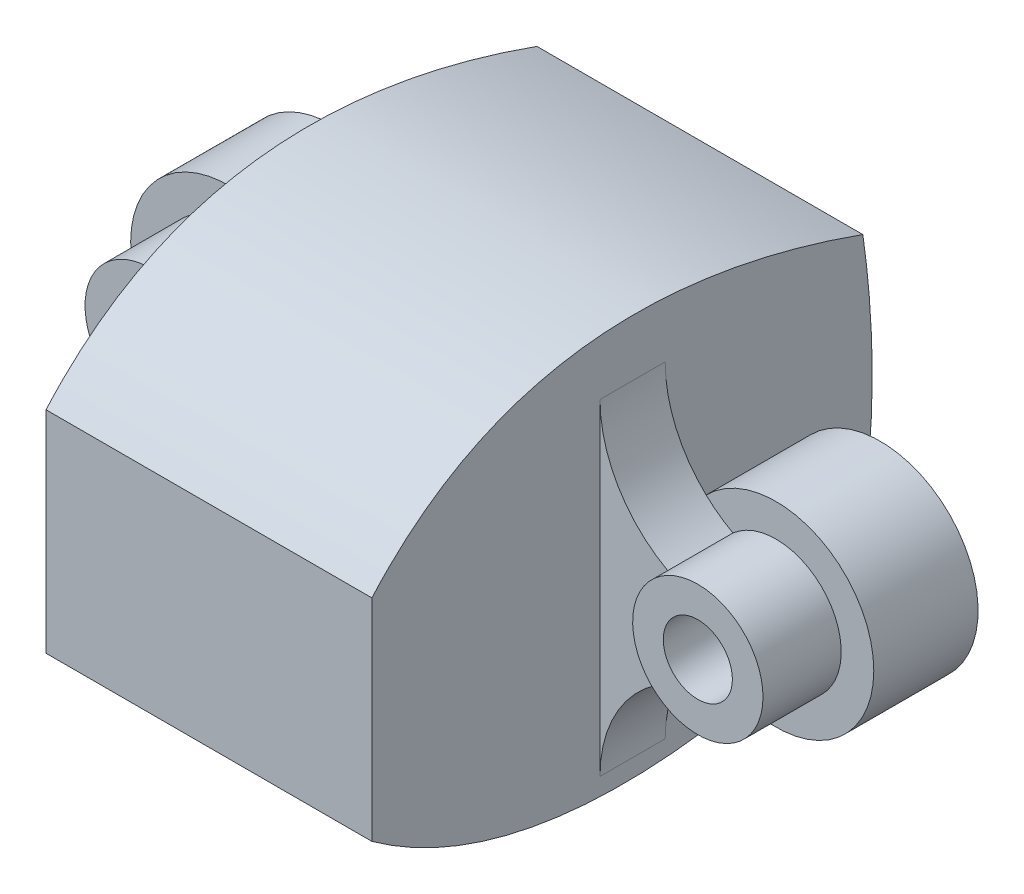
SolidWorks part; units mm, degrees
ref_plane "Front Plane" through (0, 0, 0) normal (0, 0, 1) x (1, 0, 0)
ref_plane "Top Plane" through (0, 0, 0) normal (0, 1, 0) x (1, 0, 0)
ref_plane "Right Plane" through (0, 0, 0) normal (1, 0, 0) x (0, 0, -1)
sketch "Sketch1" plane through (0, 0, 0) normal (1, 0, 0) x (0, 0, -1)
  line L0 (-19.0962, 121.2258) -> (-19.0962, 137.4045)
  spline S0 degree 2 poles (-19.0962, 137.4045) (-6.4675, 151.6991) (18.5686, 142.7118) knots 0 0 0 1 1 1
  spline S1 degree 2 poles (18.5686, 142.7118) (20.5155, 129.0566) (17.199, 118.5721) knots 0 0 0 1 1 1
  spline S2 degree 3 poles (17.199, 118.5721) (7.3552, 114.9342) (-7.5425, 112.8814) (-19.0962, 121.2258) knots 0 0 0 0 1 1 1 1
extrude "Boss-Extrude1" add sketch "Sketch1" along normal mid plane 25
sketch "Sketch3" plane through (0, 0, 0) normal (1, 0, 0) x (0, 0, -1)
  line L0 (0.9038, 129.3152) -> (-19.0962, 129.3152) construction
  line L1 (3.4038, 125.5652) -> (-1.5962, 125.5652)
  line L2 (3.4038, 125.5652) -> (3.4038, 133.0652)
  line L3 (3.4038, 133.0652) -> (-1.5962, 133.0652)
  line L4 (-1.5962, 125.5652) -> (-1.5962, 133.0652)
  line L5 (3.4038, 125.5652) -> (-1.5962, 133.0652) construction
  line L6 (3.4038, 133.0652) -> (-1.5962, 125.5652) construction
  line L7 (-19.0962, 137.4045) -> (-19.0962, 121.2258) construction
  point P4 (0.9038, 129.3152)
  dimension "D1" = 7.5
  dimension "D2" = 5
  dimension "D3" = 20
extrude "Boss-Extrude2" add sketch "Sketch3" along normal mid plane 55
sketch "Sketch4" plane through (0, 0, -3.4038) normal (0, 0, -1) x (-1, 0, 0)
  line L0 (-27.5, 129.3152) -> (27.5, 129.3152) construction
  line L1 (-27.5, 125.5652) -> (-27.5, 133.0652) construction
  line L2 (27.5, 125.5652) -> (27.5, 133.0652) construction
  circle A0 centre (-21.0048, 129.3152) radius 7.5
  circle A1 centre (21.0048, 129.3152) radius 7.5
  dimension "D1" = 15
extrude "Boss-Extrude3" add sketch "Sketch4" along normal blind 8
sketch "Sketch5" plane through (0, 0, -3.4038) normal (0, 0, 1) x (1, 0, 0)
  line L0 (0, 146.1811) -> (0, 115.4028) construction
  line L1 (12.5, 146.1811) -> (-12.5, 146.1811) construction
  line L2 (-12.5, 115.4028) -> (12.5, 115.4028) construction
  line L3 (-21.0048, 136.8152) -> (-31.11, 136.8152)
  line L4 (21.0048, 136.8152) -> (31.11, 136.8152)
  line L5 (21.0048, 136.8152) -> (21.0048, 119.4086)
  line L6 (21.0048, 119.4086) -> (31.11, 119.4086)
  line L7 (31.11, 136.8152) -> (31.11, 119.4086)
  line L8 (21.0048, 136.8152) -> (31.11, 119.4086) construction
  line L9 (21.0048, 119.4086) -> (31.11, 136.8152) construction
  line L10 (-21.0048, 136.8152) -> (-21.0048, 119.4086)
  line L11 (-21.0048, 119.4086) -> (-31.11, 119.4086)
  line L12 (-31.11, 136.8152) -> (-31.11, 119.4086)
  arc A0 (27.5, 133.0652) -> (14.5096, 133.0652) centre (21.0048, 129.3152) ccw construction
  point P10 (26.0574, 128.1119)
extrude "Cut-Extrude1" cut sketch "Sketch5" along normal through all
sketch "Sketch6" plane through (0, 0, -3.4038) normal (0, 0, 1) x (1, 0, 0)
  line L0 (21.0048, 133.0652) -> (21.0048, 125.5652) construction
  line L1 (-21.0048, 125.5652) -> (-21.0048, 133.0652) construction
  circle A0 centre (21.0048, 129.3152) radius 5
  circle A1 centre (-21.0048, 129.3152) radius 5
  dimension "D1" = 10
extrude "Boss-Extrude4" add sketch "Sketch6" along normal blind 6
fillet "Fillet1" radius 10 4 edges at (12.5, 125.5652, -0.9038) (12.5, 133.0652, -0.9038) (-12.5, 133.0652, -0.9038) (-12.5, 125.5652, -0.9038)
sketch "Sketch7" plane through (0, 0, 2.5962) normal (0, 0, 1) x (1, 0, 0)
  circle A0 centre (21.0048, 129.3152) radius 2.65
  circle A1 centre (-21.0048, 129.3152) radius 2.65
  dimension "D1" = 5.3
extrude "Cut-Extrude2" cut sketch "Sketch7" against normal blind 6
ref_plane "Plane1" through (0, 0, -0.9038) normal (0, 0, 1) x (1, 0, 0)
sketch "Sketch8" plane through (0, 0, -0.9038) normal (0, 0, 1) x (1, 0, 0)
  line L0 (21.0048, 129.3152) -> (-21.0048, 129.3152) construction
  point P4 (0, 129.3152)
move or copy body "Body-Move/Copy1" bodies to move or copy 106 copy no translate (0, -129.32, -0.9)
sketch "Sketch10" plane through (0, 0, -4.3038) normal (0, 0, -1) x (-1, 0, 0)
  line L1 (-12.5, 16.8611) -> (12.5, 16.8611)
  line L2 (-12.5, 16.8611) -> (-12.5, -13.9172)
  line L3 (-12.5, -13.9172) -> (12.5, -13.9172)
  line L4 (12.5, 16.8611) -> (12.5, -13.9172)
  line L5 (-12.5, 16.8611) -> (12.5, -13.9172) construction
  line L6 (-12.5, -13.9172) -> (12.5, 16.8611) construction
  point P4 (0, 1.4719)
extrude "Cut-Extrude3" [suppressed] cut sketch "Sketch10" along normal through all
sketch "Sketch11" plane through (0, 0, 0.6962) normal (0, 0, 1) x (1, 0, 0)
  line L0 (12.5, -13.9172) -> (12.5, -8.0942) construction
  line L1 (-12.5, 16.8611) -> (12.5, 16.8611)
  line L2 (-12.5, 16.8611) -> (-12.5, -16.4911)
  line L3 (-12.5, -16.4911) -> (12.5, -16.4911)
  line L4 (12.5, 16.8611) -> (12.5, -16.4911)
  line L5 (-12.5, 16.8611) -> (12.5, -16.4911) construction
  line L6 (-12.5, -16.4911) -> (12.5, 16.8611) construction
  point P4 (0, 0.185)
extrude "Cut-Extrude4" [suppressed] cut sketch "Sketch11" along normal through all
sketch "Sketch12" plane through (0, 0, 0.6962) normal (0, 0, 1) x (1, 0, 0)
  line L1 (-17.6976, 3.7452) -> (17.6976, 3.7452)
  line L2 (-17.6976, 3.7452) -> (-17.6976, 19.0947)
  line L3 (-17.6976, 19.0947) -> (17.6976, 19.0947)
  line L4 (17.6976, 3.7452) -> (17.6976, 19.0947)
  line L5 (-17.6976, 3.7452) -> (17.6976, 19.0947) construction
  line L6 (-17.6976, 19.0947) -> (17.6976, 3.7452) construction
  line L7 (-17.6976, -3.7548) -> (17.6976, -3.7548)
  line L8 (-17.6976, -3.7548) -> (-17.6976, -18.2927)
  line L9 (-17.6976, -18.2927) -> (17.6976, -18.2927)
  line L10 (17.6976, -3.7548) -> (17.6976, -18.2927)
  line L11 (-17.6976, -3.7548) -> (17.6976, -18.2927) construction
  line L12 (-17.6976, -18.2927) -> (17.6976, -3.7548) construction
  point P4 (0, 11.4199)
  point P12 (0, -11.0238)
extrude "Cut-Extrude5" [suppressed] cut sketch "Sketch12" against normal up to surface (5 mm away)
sketch "Sketch13" [suppressed] plane through (0, 0, -4.3038) normal (0, 0, 1) x (1, 0, 0)
  line L0 (17.6976, -3.7548) -> (-17.6976, -3.7548) construction
  line L1 (-17.6976, 3.7452) -> (17.6976, 3.7452) construction
  line L2 (14.5096, 3.7452) -> (17.6976, 3.7452)
  line L3 (17.6976, -3.7548) -> (14.5096, -3.7548)
  line L6 (-17.6976, 3.7452) -> (-14.5096, 3.7452)
  line L7 (-14.5096, -3.7548) -> (-17.6976, -3.7548)
  line L10 (14.5096, -3.7548) -> (-14.5096, -3.7548)
  line L11 (-14.5096, 3.7452) -> (14.5096, 3.7452)
  circle A0 centre (21.0048, -0.0048) radius 2.65 construction
  circle A1 centre (-21.0048, -0.0048) radius 2.65 construction
  arc A2 (14.5096, -3.7548) -> (14.5096, 3.7452) centre (21.0048, -0.0048) ccw
  arc A3 (17.6976, -3.7548) -> (17.6976, 3.7452) centre (21.0048, -0.0048) ccw
  arc A4 (14.5096, -3.7548) -> (14.5096, 3.7452) centre (21.0048, -0.0048) ccw
  arc A6 (-17.6976, 3.7452) -> (-17.6976, -3.7548) centre (-21.0048, -0.0048) ccw
  arc A7 (-14.5096, 3.7452) -> (-14.5096, -3.7548) centre (-21.0048, -0.0048) ccw
  arc A9 (-14.5096, 3.7452) -> (-14.5096, -3.7548) centre (-21.0048, -0.0048) ccw
  circle A10 centre (21.0048, -0.0048) radius 2.65
  circle A11 centre (-21.0048, -0.0048) radius 2.65
  dimension "D1" = 0
  dimension "D2" = 0
extrude "Boss-Extrude5" [suppressed] add sketch "Sketch13" along normal up to surface (6 mm away)
sketch "Sketch14" plane through (0, 0, -4.3038) normal (0, 0, -1) x (-1, 0, 0)
  line L1 (12.5, 12.5165) -> (12.5, -12.5262)
  line L2 (12.5, 12.5165) -> (12.5, -12.5262)
  arc A2 (15.6422, 5.2385) -> (15.6422, -5.2482) centre (21.0048, -0.0048) ccw
  arc A3 (12.5, 12.5165) -> (15.6422, 5.2385) centre (22.5, 12.5165) ccw
  arc A4 (15.6422, 5.2385) -> (15.6422, -5.2482) centre (21.0048, -0.0048) ccw
  arc A7 (12.5, 12.5165) -> (15.6422, 5.2385) centre (22.5, 12.5165) ccw
  arc A8 (15.6422, -5.2482) -> (12.5, -12.5262) centre (22.5, -12.5262) ccw
  arc A9 (15.6422, -5.2482) -> (12.5, -12.5262) centre (22.5, -12.5262) ccw
  dimension "D1" = 0
extrude "Boss-Extrude6" [suppressed] add sketch "Sketch14" along normal up to surface (8 mm away)
